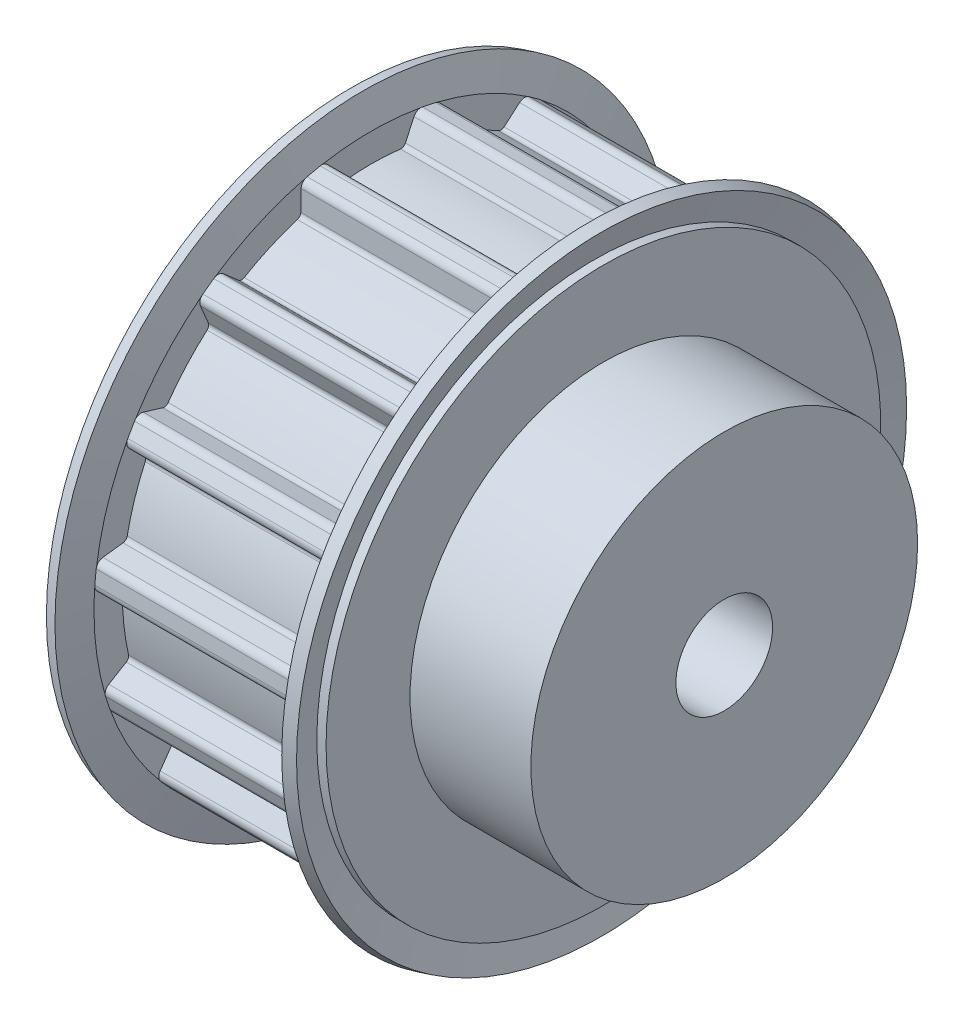
SolidWorks part; units mm, degrees
ref_plane "Plan de face" through (0, 0, 0) normal (0, 0, 1) x (1, 0, 0)
ref_plane "Plan de dessus" through (0, 0, 0) normal (0, 1, 0) x (1, 0, 0)
ref_plane "Plan de droite" through (0, 0, 0) normal (1, 0, 0) x (0, 0, -1)
ref_plane "Plane1" through (0, 0, 0) normal (0, 0, -1) x (-1, 0, 0)
sketch "Sketch1" plane through (0, 0, 0) normal (0, 0, -1) x (-1, 0, 0)
  line L0 (-21, 22.95) -> (-21, 0)
  line L1 (-21, 0) -> (0, 0)
  line L2 (0, 0) -> (0, 22.95)
  line L3 (0, 22.95) -> (-0.7647, 22.95)
  line L4 (-0.7647, 22.95) -> (-0.1508, 25.2412)
  line L5 (-0.1508, 25.2412) -> (-1.1167, 25.5)
  line L6 (-1.1167, 25.5) -> (-1.8, 22.95)
  line L7 (-1.8, 22.95) -> (-1.8, 20.6)
  line L8 (-1.8, 20.6) -> (-19.2, 20.6)
  line L9 (-19.2, 20.6) -> (-19.2, 22.95)
  line L10 (-19.2, 22.95) -> (-19.8833, 25.5)
  line L11 (-19.8833, 25.5) -> (-20.8492, 25.2412)
  line L12 (-20.8492, 25.2412) -> (-20.2353, 22.95)
  line L13 (-20.2353, 22.95) -> (-21, 22.95)
  line L14 (-21, 0) -> (0, 0) construction
revolve "Revolve1" add sketch "Sketch1" angle 360 about L14 reverse direction yes
sketch "Sketch2" plane through (21, 0, 0) normal (1, 0, 0) x (0, 0, -1)
  circle A0 centre (0, 0) radius 16
extrude "Boss-Extrude1" add sketch "Sketch2" along normal blind 10
hole_wizard "Ø8.0 (8) Diameter Hole1" positions "Sketch4" profile "Sketch3" hole size "Ø8.0" standard "ANSI Metric"
sketch "Sketch4" plane through (31, 0, 0) normal (1, 0, 0) x (0, 0, -1)
  point P0 (0, 0)
sketch "Sketch3" plane through (31, 0, 0) normal (0, 1, 0) x (0, 0, -1)
  line L0 (0, 0) -> (0, 31)
  line L1 (0, 31) -> (4, 31)
  line L2 (4, 31) -> (4, 0)
  line L5 (4, 0) -> (0, 0)
  line L11 (0, -6.35) -> (0, 107.95) construction
  dimension "Thru Hole Dia." = 8
  dimension "Thru Hole Depth" = 31
sketch "Sketch5" plane through (0, 0, 0) normal (0, 0, -1) x (-1, 0, 0)
  line L0 (-19.2, -22.95) -> (-1.8, -22.95)
rib "Rib1" sketch "Sketch5" sketch "Sketch5" thickness 2.1072 extrusion direction parallel to sketch draft on yes draft angle 13 parameters "D1"=2.1072, "D3"=13
ref_plane "Plane2" through (0, 0, 0) normal (0, -0.5878, 0.809) x (1, 0, 0)
sketch "Sketch6" plane through (0, 0, 0) normal (0, -0.5878, 0.809) x (1, 0, 0)
  line L0 (19.2, 22.95) -> (1.8, 22.95)
rib "Rib2" sketch "Sketch6" sketch "Sketch6" thickness 2.1072 extrusion direction parallel to sketch draft on yes draft angle 13 parameters "D1"=2.1072, "D3"=13
ref_plane "Plane3" through (0, 0, 0) normal (0, 0.4067, -0.9135) x (-1, 0, 0)
sketch "Sketch7" plane through (0, 0, 0) normal (0, 0.4067, -0.9135) x (-1, 0, 0)
  line L0 (-19.2, -22.95) -> (-1.8, -22.95)
rib "Rib3" sketch "Sketch7" sketch "Sketch7" thickness 2.1072 extrusion direction parallel to sketch draft on yes draft angle 13 parameters "D1"=2.1072, "D3"=13
ref_plane "Plane4" through (0, 0, 0) normal (0, -0.2079, 0.9781) x (1, 0, 0)
sketch "Sketch8" plane through (0, 0, 0) normal (0, -0.2079, 0.9781) x (1, 0, 0)
  line L0 (19.2, 22.95) -> (1.8, 22.95)
rib "Rib4" sketch "Sketch8" sketch "Sketch8" thickness 2.1072 extrusion direction parallel to sketch draft on yes draft angle 13 parameters "D1"=2.1072, "D3"=13
ref_plane "Plane5" through (0, 0, 0) normal (0, 0.9945, 0.1045) x (-1, 0, 0)
sketch "Sketch9" plane through (0, 0, 0) normal (0, 0.9945, 0.1045) x (-1, 0, 0)
  line L0 (-19.2, -22.95) -> (-1.8, -22.95)
rib "Rib5" sketch "Sketch9" sketch "Sketch9" thickness 2.1072 extrusion direction parallel to sketch draft on yes draft angle 13 parameters "D1"=2.1072, "D3"=13
ref_plane "Plane6" through (0, 0, 0) normal (0, 0.7431, -0.6691) x (-1, 0, 0)
sketch "Sketch10" plane through (0, 0, 0) normal (0, 0.7431, -0.6691) x (-1, 0, 0)
  line L0 (-19.2, -22.95) -> (-1.8, -22.95)
rib "Rib6" sketch "Sketch10" sketch "Sketch10" thickness 2.1072 extrusion direction parallel to sketch draft on yes draft angle 13 parameters "D1"=2.1072, "D3"=13
ref_plane "Plane7" through (0, 0, 0) normal (0, -0.4067, -0.9135) x (1, 0, 0)
sketch "Sketch11" plane through (0, 0, 0) normal (0, -0.4067, -0.9135) x (1, 0, 0)
  line L0 (19.2, 22.95) -> (1.8, 22.95)
rib "Rib7" sketch "Sketch11" sketch "Sketch11" thickness 2.1072 extrusion direction parallel to sketch draft on yes draft angle 13 parameters "D1"=2.1072, "D3"=13
ref_plane "Plane8" through (0, 0, 0) normal (0, 0.9511, -0.309) x (-1, 0, 0)
sketch "Sketch12" plane through (0, 0, 0) normal (0, 0.9511, -0.309) x (-1, 0, 0)
  line L0 (-19.2, -22.95) -> (-1.8, -22.95)
rib "Rib8" sketch "Sketch12" sketch "Sketch12" thickness 2.1072 extrusion direction parallel to sketch draft on yes draft angle 13 parameters "D1"=2.1072, "D3"=13
ref_plane "Plane9" through (0, 0, 0) normal (0, 0.2079, 0.9781) x (-1, 0, 0)
sketch "Sketch13" plane through (0, 0, 0) normal (0, 0.2079, 0.9781) x (-1, 0, 0)
  line L0 (-19.2, -22.95) -> (-1.8, -22.95)
rib "Rib9" sketch "Sketch13" sketch "Sketch13" thickness 2.1072 extrusion direction parallel to sketch draft on yes draft angle 13 parameters "D1"=2.1072, "D3"=13
ref_plane "Plane10" through (0, 0, 0) normal (0, -0.866, 0.5) x (1, 0, 0)
sketch "Sketch14" plane through (0, 0, 0) normal (0, -0.866, 0.5) x (1, 0, 0)
  line L0 (19.2, 22.95) -> (1.8, 22.95)
rib "Rib10" sketch "Sketch14" sketch "Sketch14" thickness 2.1072 extrusion direction parallel to sketch draft on yes draft angle 13 parameters "D1"=2.1072, "D3"=13
ref_plane "Plane11" through (0, 0, 0) normal (0, -0.9511, -0.309) x (1, 0, 0)
sketch "Sketch15" plane through (0, 0, 0) normal (0, -0.9511, -0.309) x (1, 0, 0)
  line L0 (19.2, 22.95) -> (1.8, 22.95)
rib "Rib11" sketch "Sketch15" sketch "Sketch15" thickness 2.1072 extrusion direction parallel to sketch draft on yes draft angle 13 parameters "D1"=2.1072, "D3"=13
ref_plane "Plane12" through (0, 0, 0) normal (0, 0.866, 0.5) x (-1, 0, 0)
sketch "Sketch16" plane through (0, 0, 0) normal (0, 0.866, 0.5) x (-1, 0, 0)
  line L0 (-19.2, -22.95) -> (-1.8, -22.95)
rib "Rib12" sketch "Sketch16" sketch "Sketch16" thickness 2.1072 extrusion direction parallel to sketch draft on yes draft angle 13 parameters "D1"=2.1072, "D3"=13
ref_plane "Plane13" through (0, 0, 0) normal (0, -0.9945, 0.1045) x (1, 0, 0)
sketch "Sketch17" plane through (0, 0, 0) normal (0, -0.9945, 0.1045) x (1, 0, 0)
  line L0 (19.2, 22.95) -> (1.8, 22.95)
rib "Rib13" sketch "Sketch17" sketch "Sketch17" thickness 2.1072 extrusion direction parallel to sketch draft on yes draft angle 13 parameters "D1"=2.1072, "D3"=13
ref_plane "Plane14" through (0, 0, 0) normal (0, -0.7431, -0.6691) x (1, 0, 0)
sketch "Sketch18" plane through (0, 0, 0) normal (0, -0.7431, -0.6691) x (1, 0, 0)
  line L0 (19.2, 22.95) -> (1.8, 22.95)
rib "Rib14" sketch "Sketch18" sketch "Sketch18" thickness 2.1072 extrusion direction parallel to sketch draft on yes draft angle 13 parameters "D1"=2.1072, "D3"=13
ref_plane "Plane15" through (0, 0, 0) normal (0, 0.5878, 0.809) x (-1, 0, 0)
sketch "Sketch19" plane through (0, 0, 0) normal (0, 0.5878, 0.809) x (-1, 0, 0)
  line L0 (-19.2, -22.95) -> (-1.8, -22.95)
rib "Rib15" sketch "Sketch19" sketch "Sketch19" thickness 2.1072 extrusion direction parallel to sketch draft on yes draft angle 13 parameters "D1"=2.1072, "D3"=13
fillet "Fillet1" radius 0.4 30 edges at (10.5, 0.5448, 20.5928) (10.5, 8.8735, -18.5909) (10.5, -14.9389, -14.1841) (10.5, 0.5448, -20.5928) (10.5, -19.4166, -6.8817) (10.5, -20.5369, 1.6107) (10.5, 8.8735, 18.5909) (10.5, -19.4166, 6.8817) (10.5, 11.6634, 16.9801) (10.5, -4.8144, -20.0295) (10.5, 17.5615, 10.7682) (10.5, 20.423, -2.6943) (10.5, 20.423, 2.6943) (10.5, -18.1063, 9.8246) (10.5, 19.7533, -5.8454) (10.5, -14.9389, 14.1841) (10.5, 3.7486, 20.2561) (10.5, 15.668, -13.3744) (10.5, -18.1063, -9.8246) (10.5, -7.8782, -19.034) (10.5, 15.668, 13.3744) (10.5, -12.5449, 16.3397) (10.5, 3.7486, -20.2561) (10.5, -7.8782, 19.034) (10.5, 19.7533, 5.8454) (10.5, -12.5449, -16.3397) (10.5, 17.5615, -10.7682) (10.5, 11.6634, -16.9801) (10.5, -4.8144, 20.0295) (10.5, -20.5369, -1.6107) tangent propagation no
fillet "Fillet2" radius 0.625 30 edges at (10.5, -22.95, -1.0536) (10.5, 1.3511, 22.9344) (10.5, -16.1395, 16.3502) (10.5, 22.6675, -3.741) (10.5, 19.1862, 12.6373) (10.5, 22.2294, -5.8022) (10.5, -21.3944, 8.3721) (10.5, 19.1862, -12.6373) (10.5, -8.094, 21.5012) (10.5, 17.9476, -14.3421) (10.5, 12.3875, 19.3485) (10.5, 12.3875, -19.3485) (10.5, 3.4468, 22.7141) (10.5, 3.4468, -22.7141) (10.5, -22.95, 1.0536) (10.5, 1.3511, -22.9344) (10.5, -20.5373, 10.2971) (10.5, -6.0899, -22.1523) (10.5, -14.5736, 17.7602) (10.5, -8.094, -21.5012) (10.5, -6.0899, 22.1523) (10.5, -14.5736, -17.7602) (10.5, 10.5625, 20.4021) (10.5, -16.1395, -16.3502) (10.5, 17.9476, 14.3421) (10.5, -20.5373, -10.2971) (10.5, 22.2294, 5.8022) (10.5, -21.3944, -8.3721) (10.5, 22.6675, 3.741) (10.5, 10.5625, -20.4021) tangent propagation no
